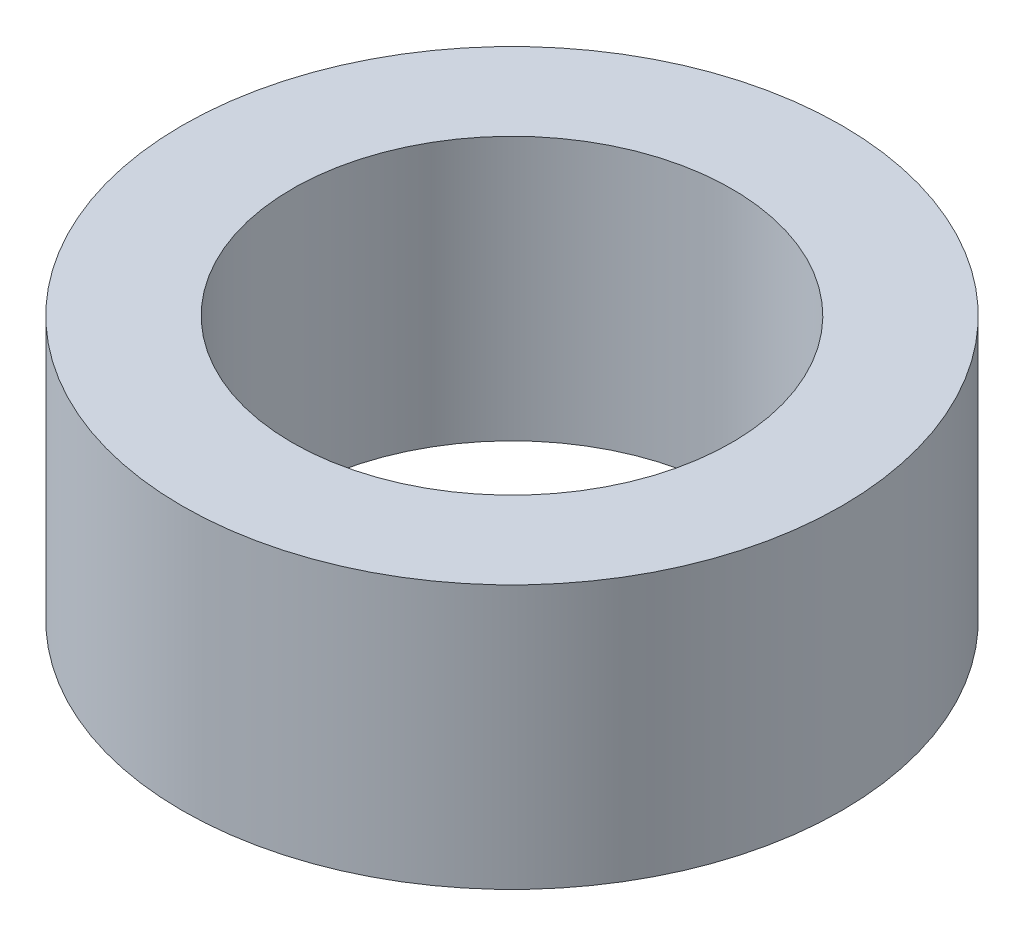
SolidWorks part; units mm, degrees
ref_plane "Front Plane" through (0, 0, 0) normal (0, 0, 1) x (1, 0, 0)
ref_plane "Top Plane" through (0, 0, 0) normal (0, 1, 0) x (1, 0, 0)
ref_plane "Right Plane" through (0, 0, 0) normal (1, 0, 0) x (0, 0, -1)
sketch "Sketch1" plane through (0, 0, 0) normal (0, 1, 0) x (1, 0, 0)
  circle A0 centre (0, 0) radius 30
  dimension "FLANGE_OD" = 60
extrude "Boss-Extrude1" add sketch "Sketch1" along normal blind 24
sketch "Sketch2" plane through (0, 0, 0) normal (0, 1, 0) x (1, 0, 0)
  circle A0 centre (0, 0) radius 20
  dimension "BORE_D" = 40
extrude "Cut-Extrude1" cut sketch "Sketch2" along normal through all
sketch "Sketch3" plane through (0, 24, 0) normal (0, 1, 0) x (1, 0, 0)
  circle A0 centre (0, 0) radius 11.266 construction
  circle A1 centre (-11.266, 0) radius 1.5262
  dimension "BOLT_D" = 3.0524
  dimension "BOLT_PCD" = 22.532
extrude "Cut-Extrude2" cut sketch "Sketch3" against normal blind 22.8471 rebuild error yes
pattern_circular "CirPattern1" count 5 over 360 rebuild error yes
